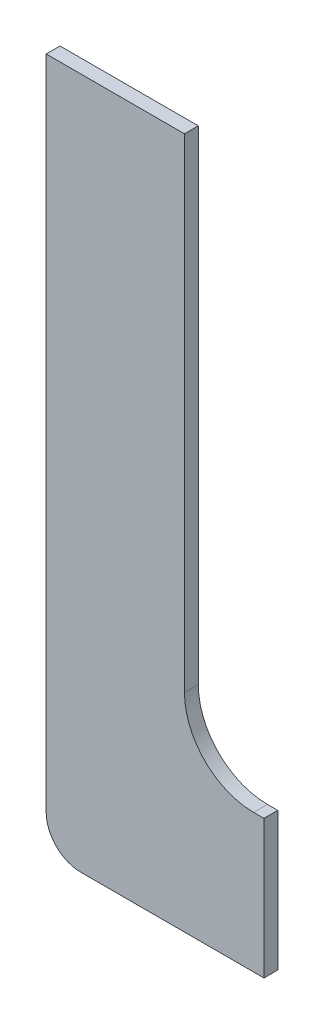
SolidWorks part; units mm, degrees
ref_plane "前视基准面" through (0, 0, 0) normal (0, 0, 1) x (1, 0, 0)
ref_plane "上视基准面" through (0, 0, 0) normal (0, 1, 0) x (1, 0, 0)
ref_plane "右视基准面" through (0, 0, 0) normal (1, 0, 0) x (0, 0, -1)
sketch "草图1" plane through (0, 0, 0) normal (0, 0, 1) x (1, 0, 0)
  line L0 (0, 0) -> (-31.5, 0)
  line L1 (-31.5, 0) -> (-31.5, 100)
  line L2 (-31.5, 100) -> (-11.5, 100)
  line L3 (-11.5, 100) -> (-11.5, 20)
  line L4 (-11.5, 20) -> (0, 20)
  line L5 (0, 20) -> (0, 0)
  point P4 (-16.3351, 46.2215)
  dimension "D1" = 100
  dimension "D2" = 31.5
  dimension "D3" = 20
  dimension "D4" = 20
extrude "凸台-拉伸1" add sketch "草图1" along normal blind 2
fillet "圆角1" radius 10 1 edges at (-11.5, 20, 1)
fillet "圆角2" radius 5 1 edges at (-31.5, 0, 1)
